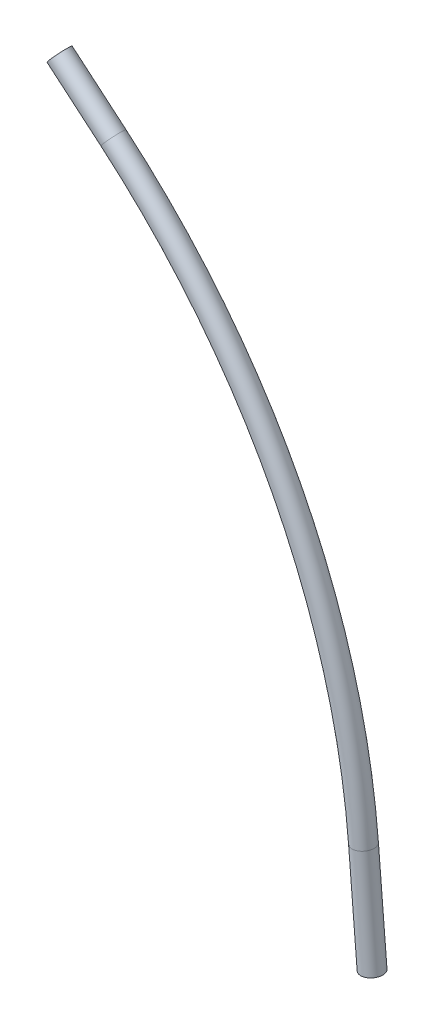
SolidWorks part; units mm, degrees
material "Aço cromo inoxidável"
ref_plane "Plano frontal" through (0, 0, 0) normal (0, 0, 1) x (1, 0, 0)
ref_plane "Plano superior" through (0, 0, 0) normal (0, 1, 0) x (1, 0, 0)
ref_plane "Plano direito" through (0, 0, 0) normal (1, 0, 0) x (0, 0, -1)
sketch "Esboço1" plane through (0, 0, 0) normal (0, 0, 1) x (1, 0, 0)
  line L0 (-120.5898, 314.7842) -> (-135.8656, 327.6935)
  line L1 (-122.8942, 312.0575) -> (-118.2855, 317.511) construction
  line L2 (-49.675, 176.958) -> (-47.2406, 147.0569)
  line L4 (-83.2823, 278.4093) -> (-88.1128, 274.8503) construction
  line L6 (-137.802, 325.4022) -> (-133.9292, 329.9849) construction
  arc A2 (-120.5898, 314.7842) -> (-49.675, 176.958) centre (-250.9097, 160.5747) cw
  point P2 (-85.6976, 276.6298)
  dimension "D1" = 155
  dimension "D2" = 30
sweep "Varredura1" add path "Esboço1" circular profile diameter 6 parameters "D3"=6
chamfer "Chanfro1" [suppressed] distance 0.5 angle 45
